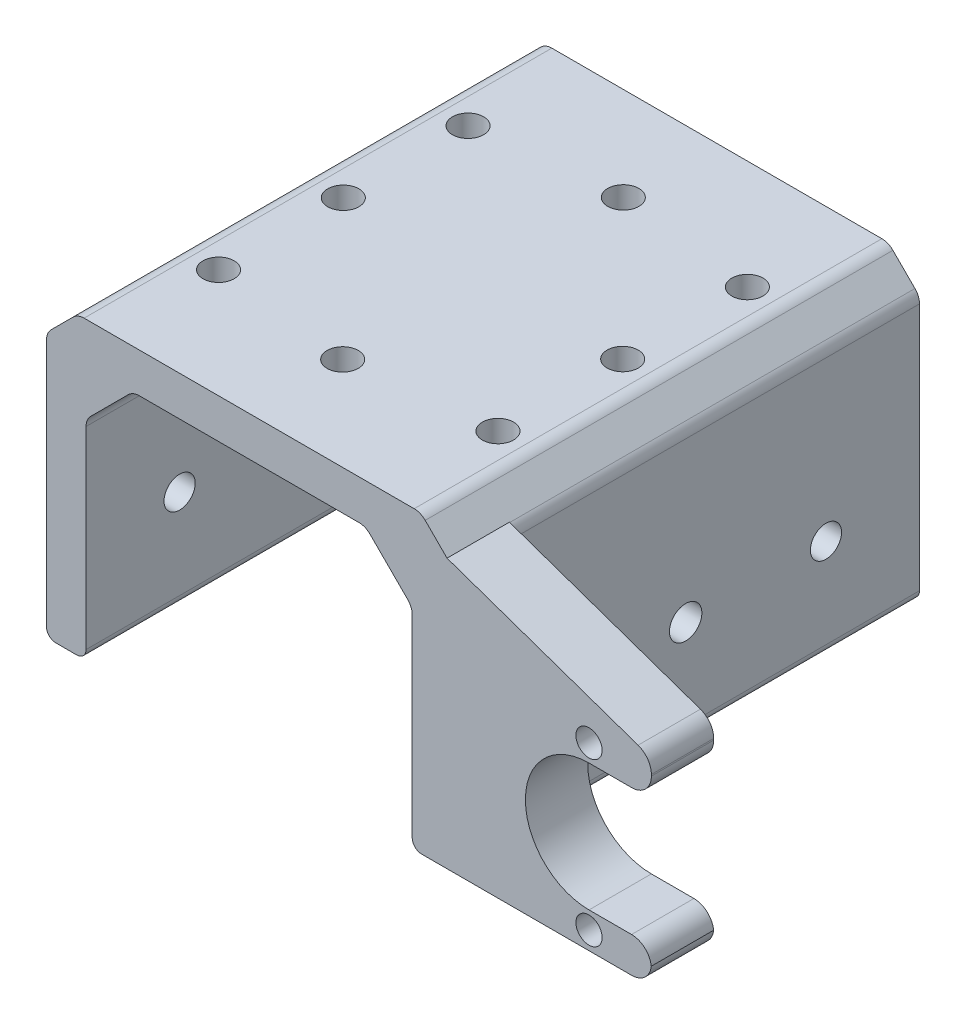
SolidWorks part; units mm, degrees
ref_plane "Front Plane" through (0, 0, 0) normal (0, 0, 1) x (1, 0, 0)
ref_plane "Top Plane" through (0, 0, 0) normal (0, 1, 0) x (1, 0, 0)
ref_plane "Right Plane" through (0, 0, 0) normal (1, 0, 0) x (0, 0, -1)
sketch "Sketch1" plane through (0, 0, 0) normal (0, 0, 1) x (1, 0, 0)
  line L0 (6.35, 33.52) -> (13.85, 41.02)
  line L1 (0, 0) -> (6.35, 0)
  line L2 (0, 0) -> (0, 41.02)
  line L4 (6.35, 0) -> (6.35, 33.52)
  line L5 (0, 0) -> (6.35, 41.02) construction
  line L6 (0, 41.02) -> (6.35, 0) construction
  line L7 (13.85, 41.02) -> (51.15, 41.02)
  line L8 (0, 41.02) -> (0, 47.37)
  line L9 (0, 47.37) -> (65, 47.37)
  line L10 (65, 41.02) -> (65, 47.37)
  line L11 (0, 41.02) -> (65, 47.37) construction
  line L12 (0, 47.37) -> (65, 41.02) construction
  line L14 (65, 41.02) -> (65, 0)
  line L15 (65, 0) -> (58.65, 0)
  line L16 (58.65, 33.52) -> (58.65, 0)
  line L17 (65, 41.02) -> (58.65, 0) construction
  line L18 (65, 0) -> (58.65, 41.02) construction
  line L19 (51.15, 41.02) -> (58.65, 33.52)
  line L20 (13.85, 41.02) -> (6.35, 41.02) construction
  line L21 (6.35, 41.02) -> (6.35, 33.52) construction
  line L22 (51.15, 41.02) -> (58.65, 41.02) construction
  line L23 (58.65, 41.02) -> (58.65, 33.52) construction
  point P4 (3.175, 20.51)
  point P9 (32.5, 44.195)
  point P13 (61.825, 20.51)
  dimension "D1" = 6.35
  dimension "D2" = 41.02
  dimension "D3" = 52.3
  dimension "D4" = 7.5
  dimension "D5" = 7.5
  dimension "D6" = 7.5
  dimension "D7" = 7.5
extrude "Boss-Extrude1" add sketch "Sketch1" along normal blind 75 contours L2 L8 L9 L10 L14 L15 L16 L19 L7 L0 L4 L1
sketch "Sketch2" plane through (0, 0, 0) normal (-1, 0, 0) x (0, 0, 1)
  line L0 (75, 41.02) -> (0, 41.02) construction
  line L1 (75, 41.02) -> (0, 41.02) construction
  line L2 (0, 15.87) -> (75, 15.87) construction
  line L3 (0, 0) -> (0, 47.37) construction
  line L4 (75, 0) -> (75, 47.37) construction
  line L5 (37.5, 0) -> (37.5, 47.37) construction
  line L6 (75, 0) -> (0, 0) construction
  line L7 (75, 47.37) -> (0, 47.37) construction
  point P2 (15, 15.87)
  point P15 (60, 15.87)
  dimension "D1" = 25.15
  dimension "D2" = 22.5
  dimension "D3" = 22.5
hole_wizard "M6x1.0 Tapped Hole1" positions "Sketch3" profile "Sketch4" tap size "M6x1.0" standard "Autoliv NAM Metric" end condition up to next
sketch "Sketch3" plane through (0, 0, 0) normal (-1, 0, 0) x (0, 0, 1)
  point P1 (60, 15.87)
  point P3 (15, 15.87)
sketch "Sketch4" plane through (0, 15.87, 60) normal (0, 1, 0) x (0, 0, 1)
  line L0 (0, 0) -> (0, 65)
  line L1 (0, 65) -> (2.5, 65)
  line L2 (2.5, 65) -> (2.5, 0)
  line L5 (2.5, 0) -> (0, 0)
  line L11 (0, -6.35) -> (0, 107.95) construction
  dimension "Thru Tap Drill Dia." = 5
  dimension "Thru Tap Drill Depth" = 65
cosmetic thread "Hole Thread1" parameters "D2"=6
cosmetic thread "Hole Thread2" parameters "D2"=6
ref_plane "Plane1" through (32.5, 0, 0) normal (-1, 0, 0) x (0, 0, 1)
mirror "Mirror1" about plane through (32.5, 0, 0) normal (-1, 0, 0) of "M6x1.0 Tapped Hole1"
sketch "Sketch5" plane through (0, 47.37, 0) normal (0, 1, 0) x (1, 0, 0)
  line L0 (32.5, -75) -> (32.5, 0) construction
  line L1 (0, -75) -> (65, -75) construction
  line L2 (0, 0) -> (65, 0) construction
  line L3 (0, -37.5) -> (65, -37.5) construction
  line L4 (0, -75) -> (0, 0) construction
  line L5 (65, -75) -> (65, 0) construction
  point P12 (32.5, -60)
  point P13 (32.5, -15)
  dimension "D1" = 22.5
  dimension "D2" = 22.5
hole_wizard "M6x1.0 Tapped Hole2" positions "Sketch6" profile "Sketch7" tap size "M6x1.0" standard "Autoliv NAM Metric" end condition up to next
sketch "Sketch6" plane through (0, 47.37, 0) normal (0, 1, 0) x (1, 0, 0)
  point P1 (32.5, -15)
  point P3 (32.5, -60)
sketch "Sketch7" plane through (32.5, 47.37, 15) normal (1, 0, 0) x (0, 0, 1)
  line L0 (0, 0) -> (0, 6.35)
  line L1 (0, 6.35) -> (2.5, 6.35)
  line L2 (2.5, 6.35) -> (2.5, 0)
  line L5 (2.5, 0) -> (0, 0)
  line L11 (0, -6.35) -> (0, 107.95) construction
  dimension "Thru Tap Drill Dia." = 5
  dimension "Thru Tap Drill Depth" = 6.35
cosmetic thread "Hole Thread3" parameters "D2"=6
cosmetic thread "Hole Thread4" parameters "D2"=6
sketch "Sketch8" plane through (0, 0, 0) normal (-1, 0, 0) x (0, 0, 1)
  line L0 (17.5, 15.87) -> (57.5, 15.87) construction
  line L1 (37.5, 0) -> (37.5, 47.37) construction
  line L2 (75, 0) -> (0, 0) construction
  line L3 (75, 47.37) -> (0, 47.37) construction
  circle A0 centre (15, 15.87) radius 2.5 construction
  circle A1 centre (60, 15.87) radius 2.5 construction
  circle A2 centre (37.5, 15.87) radius 2.6
  dimension "D1" = 5.2
extrude "Cut-Extrude1" cut sketch "Sketch8" against normal through all contours A2
sketch "Sketch9" plane through (65, 0, 0) normal (1, 0, 0) x (0, 0, -1)
  line L6 (-75, 0) -> (-65, 0)
  line L7 (-75, 0) -> (-75, 31.74)
  line L8 (-75, 31.74) -> (-65, 31.74)
  line L9 (-65, 0) -> (-65, 31.74)
  line L10 (-75, 0) -> (-65, 31.74) construction
  line L11 (-75, 31.74) -> (-65, 0) construction
  circle A5 centre (-60, 15.87) radius 2.5 construction
  circle A6 centre (-70, 2.87) radius 1.6 construction
  circle A7 centre (-70, 28.87) radius 1.6 construction
  point P10 (-70, 2.87)
  point P11 (-70, 28.87)
  point P13 (-70, 15.87)
  dimension "D3" = 13
  dimension "D5" = 3.2
  dimension "D1" = 2.87
  dimension "D2" = 26
  dimension "D4" = 10
extrude "Boss-Extrude2" add sketch "Sketch9" along normal blind 32 contours L9 L8 L7 L6
sketch "Sketch10" plane through (0, 0, 65) normal (0, 0, -1) x (-1, 0, 0)
  line L0 (-87, 2.87) -> (-87, 28.87) construction
  line L3 (-97, 15.87) -> (-58.65, 15.87) construction
  line L4 (-97, 0) -> (-97, 31.74) construction
  line L5 (-58.65, 33.52) -> (-58.65, 0) construction
  line L6 (-87, 26.07) -> (-97, 26.07)
  line L7 (-87, 5.67) -> (-97, 5.67)
  line L8 (-97, 5.67) -> (-97, 26.07)
  circle A0 centre (-87, 28.87) radius 2.1
  circle A1 centre (-87, 2.87) radius 2.1
  arc A2 (-87, 5.67) -> (-87, 26.07) centre (-87, 15.87) ccw
  dimension "D3" = 4.2
  dimension "D4" = 20.4
  dimension "D1" = 26
  dimension "D2" = 13
  dimension "D5" = 10
extrude "Cut-Extrude2" cut sketch "Sketch10" against normal up to next
sketch "Sketch11" plane through (0, 0, 75) normal (0, 0, 1) x (1, 0, 0)
  line L0 (97, 31.74) -> (65, 42.87)
  line L1 (65, 42.87) -> (65, 31.74)
  line L2 (65, 31.74) -> (97, 31.74)
  line L3 (65, 47.37) -> (65, 31.74) construction
  dimension "D1" = 4.5
extrude "Boss-Extrude3" add sketch "Sketch11" against normal up to surface (10 mm away) contours L0 L1 L2 up to face at (84.9, 28.87, 65)
sketch "Sketch12" plane through (0, 47.37, 0) normal (0, 1, 0) x (1, 0, 0)
  line L0 (51.15, -75) -> (58.65, -75) construction
  line L1 (6.35, -75) -> (13.85, -75) construction
  line L2 (51.15, -75) -> (58.65, -75) construction
  line L3 (6.35, -75) -> (13.85, -75) construction
  line L4 (51.15, 0) -> (58.65, 0) construction
  line L5 (6.35, 0) -> (13.85, 0) construction
  line L6 (51.15, 0) -> (58.65, 0) construction
  line L7 (6.35, 0) -> (13.85, 0) construction
  line L8 (54.9, -75) -> (54.9, 0) construction
  line L9 (10.1, -75) -> (10.1, 0) construction
  line L10 (0, -37.5) -> (65, -37.5) construction
  line L11 (0, -75) -> (0, 0) construction
  line L12 (65, -75) -> (65, 0) construction
  circle A0 centre (54.9, -37.5) radius 3.2 construction
  circle A1 centre (54.9, -57.5) radius 3.2 construction
  circle A2 centre (54.9, -17.5) radius 3.2 construction
  dimension "D1" = 6.4
  dimension "D2" = 20
  dimension "D3" = 20
hole_wizard "M6x1.0 Tapped Hole3" positions "Sketch13" profile "Sketch14" tap size "M6x1.0" standard "Autoliv NAM Metric" end condition up to next
sketch "Sketch13" plane through (0, 47.37, 0) normal (0, 1, 0) x (1, 0, 0)
  point P0 (54.9, -57.5)
  point P3 (54.9, -37.5)
  point P6 (54.9, -17.5)
sketch "Sketch14" plane through (54.9, 47.37, 57.5) normal (1, 0, 0) x (0, 0, 1)
  line L0 (0, 0) -> (0, 13.851)
  line L1 (0, 13.851) -> (2.5, 13.851)
  line L2 (2.5, 13.851) -> (2.5, 0)
  line L5 (2.5, 0) -> (0, 0)
  line L11 (0, -6.35) -> (0, 107.95) construction
  dimension "Thru Tap Drill Dia." = 5
  dimension "Thru Tap Drill Depth" = 13.851
cosmetic thread "Hole Thread5" parameters "D2"=6
cosmetic thread "Hole Thread6" parameters "D2"=6
cosmetic thread "Hole Thread7" parameters "D2"=6
mirror "Mirror2" about plane through (32.5, 0, 0) normal (-1, 0, 0) of "M6x1.0 Tapped Hole3"
fillet "Fillet1" radius 3.175 4 edges at (97, 31.74, 70) (97, 26.07, 70) (97, 5.67, 70) (97, 0, 70) tangent propagation no
chamfer "Chamfer1" distance 5 angle 45 2 edges at (0, 47.37, 37.5) (65, 47.37, 37.5)
fillet "Fillet2" radius 2.5 8 edges at (6.35, 33.52, 37.5) (13.85, 41.02, 37.5) (51.15, 41.02, 37.5) (58.65, 33.52, 37.5) (0, 42.37, 37.5) (5, 47.37, 37.5) (65, 42.37, 32.5) (60, 47.37, 37.5)
fillet "Fillet3" radius 1.5 4 edges at (0, 0, 37.5) (6.35, 0, 37.5) (58.65, 0, 37.5) (65, 0, 32.5)
